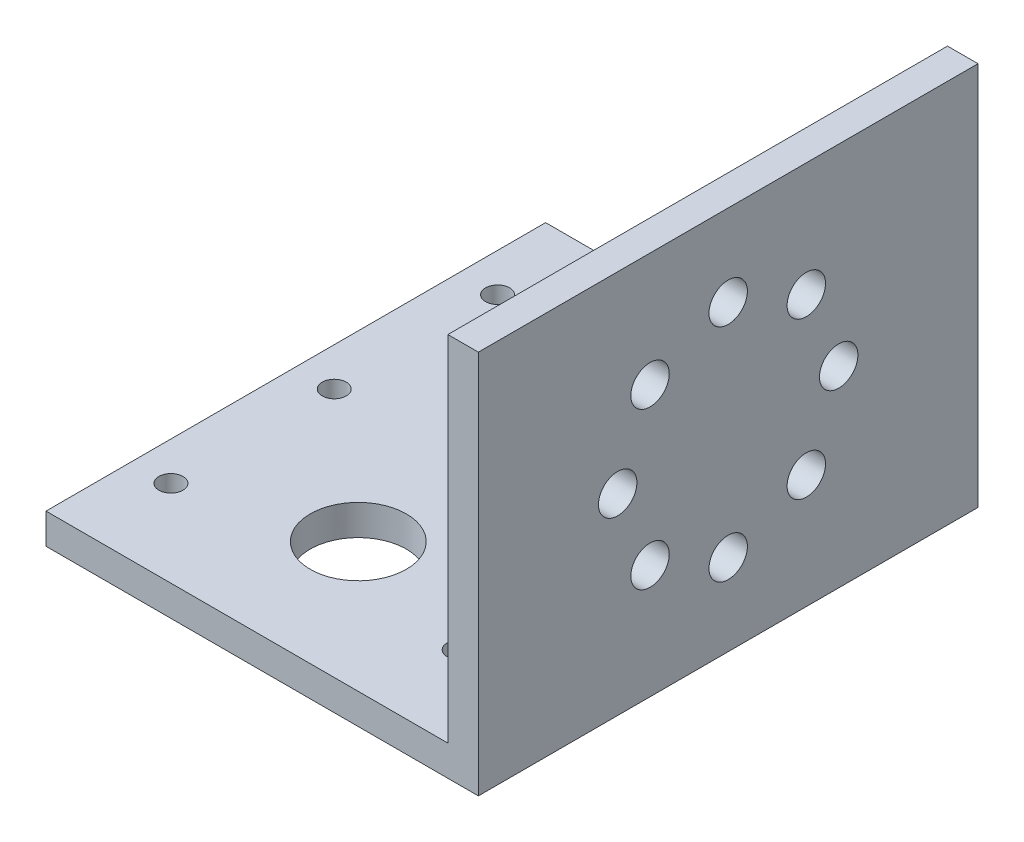
SolidWorks part; units mm, degrees
ref_plane "Front Plane" through (0, 0, 0) normal (0, 0, 1) x (1, 0, 0)
ref_plane "Top Plane" through (0, 0, 0) normal (0, 1, 0) x (1, 0, 0)
ref_plane "Right Plane" through (0, 0, 0) normal (1, 0, 0) x (0, 0, -1)
sketch "Sketch1" plane through (0, 0, 0) normal (0, 0, 1) x (1, 0, 0)
  line L0 (0, 0) -> (0, 36.825)
  line L1 (0, 36.825) -> (3.175, 36.825)
  line L2 (3.175, 36.825) -> (3.175, -3.175)
  line L3 (3.175, -3.175) -> (-41.825, -3.175)
  line L4 (-41.825, -3.175) -> (-41.825, 0)
  line L5 (-41.825, 0) -> (0, 0)
  dimension "D1" = 3.175
  dimension "D2" = 3.175
  dimension "D3" = 45
  dimension "D4" = 40
extrude "Boss-Extrude1" add sketch "Sketch1" along normal blind 52
sketch "Sketch2" plane through (3.175, 0, 0) normal (1, 0, 0) x (0, 0, -1)
  line L0 (-26, 36.825) -> (-26, -3.175) construction
  line L1 (-52, 36.825) -> (0, 36.825) construction
  line L2 (-52, -3.175) -> (0, -3.175) construction
  circle A0 centre (-26, 28.325) radius 2
  circle A1 centre (-26, 16.825) radius 11.5 construction
  circle A2 centre (-17.8683, 24.9567) radius 2
  circle A3 centre (-14.5, 16.825) radius 2
  circle A4 centre (-17.8683, 8.6933) radius 2
  circle A5 centre (-26, 5.325) radius 2
  circle A6 centre (-34.1317, 8.6933) radius 2
  circle A7 centre (-37.5, 16.825) radius 2
  circle A8 centre (-34.1317, 24.9567) radius 2
  point P27 (-26, 16.825)
  dimension "D1" = 4
  dimension "D2" = 23
  dimension "D3" = 8
extrude "Cut-Extrude1" cut sketch "Sketch2" against normal through all
sketch "Sketch3" plane through (0, -3.175, 0) normal (0, -1, 0) x (-1, 0, 0)
  line L2 (41.825, 0) -> (-3.175, 0) construction
  line L3 (41.825, -52) -> (41.825, 0) construction
  circle A0 centre (7.825, -43) radius 1.25
  circle A1 centre (37.825, -43) radius 1.25
  circle A2 centre (37.825, -26) radius 1.25
  circle A3 centre (37.825, -9) radius 1.25
  circle A4 centre (7.825, -26) radius 1.25
  circle A5 centre (7.825, -9) radius 1.25
  circle A6 centre (22.825, -38.5) radius 5
  dimension "D1" = 2.5
  dimension "D6" = 10
  dimension "D7" = 4.5
  dimension "D2" = 9
  dimension "D3" = 4
  dimension "D8" = 15
  dimension "D4" = 2
  dimension "D5" = 3
extrude "Cut-Extrude2" cut sketch "Sketch3" against normal through all
